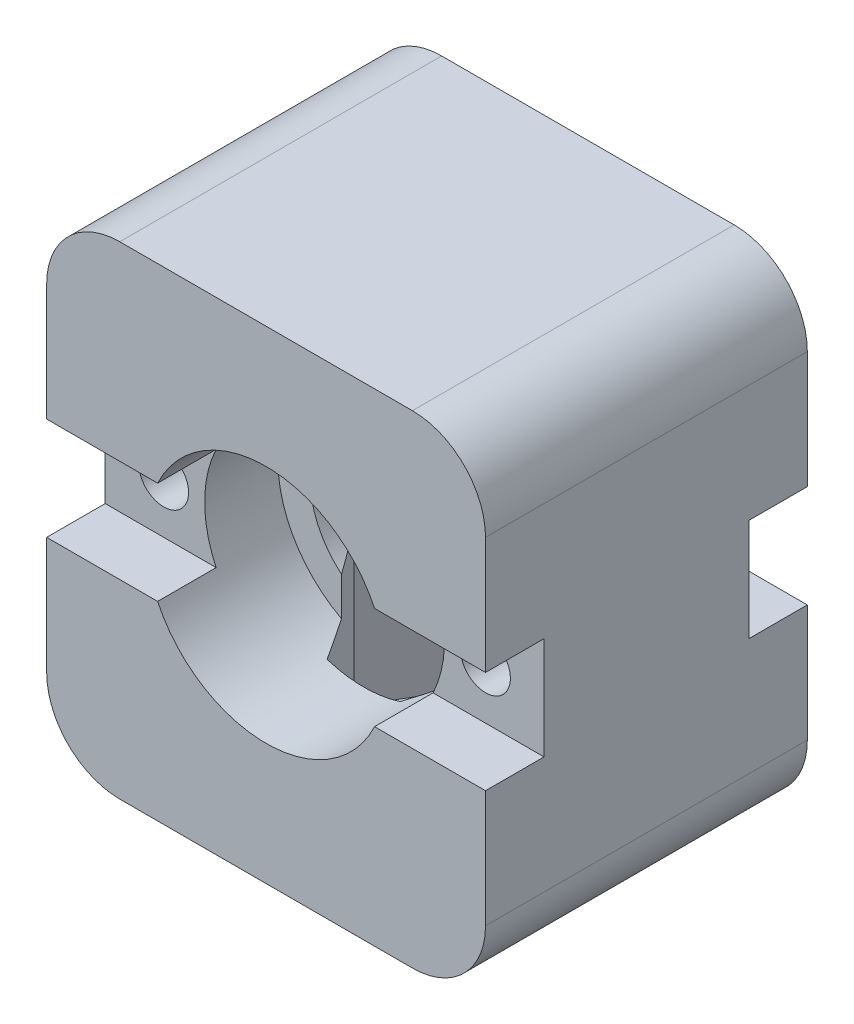
SolidWorks part; units mm, degrees
material "PLA"
ref_plane "Alzado" through (0, 0, 0) normal (0, 0, 1) x (1, 0, 0)
ref_plane "Planta" through (0, 0, 0) normal (0, 1, 0) x (1, 0, 0)
ref_plane "Vista lateral" through (0, 0, 0) normal (1, 0, 0) x (0, 0, -1)
sketch "Croquis2" plane through (0, 0, 0) normal (0, 0, 1) x (1, 0, 0)
  line L0 (-15, -1.5) -> (-15, 1.5)
  line L1 (10, -16.5) -> (-10, -16.5)
  line L2 (15, -11.5) -> (15, -1.5)
  line L3 (10, 16.5) -> (-10, 16.5)
  line L4 (-15, -11.5) -> (-15, -1.5)
  line L5 (15, -16.5) -> (-15, 16.5) construction
  line L6 (15, 16.5) -> (-15, -16.5) construction
  line L9 (-15, 1.5) -> (-15, 11.5)
  line L10 (0, 27.7977) -> (0, -27.7977) construction
  line L13 (15, 1.5) -> (15, 11.5)
  line L14 (15, -1.5) -> (15, 1.5)
  arc A0 (-15, -11.5) -> (-10, -16.5) centre (-10, -11.5) ccw
  arc A1 (10, -16.5) -> (15, -11.5) centre (10, -11.5) ccw
  arc A2 (15, 11.5) -> (10, 16.5) centre (10, 11.5) ccw
  arc A3 (-15, 11.5) -> (-10, 16.5) centre (-10, 11.5) cw
  point P0 (0, 0)
  point P30 (0, 0)
  dimension "D3" = 5
  dimension "D1" = 30
  dimension "D2" = 33
extrude "Saliente-Extruir2" add sketch "Croquis2" along normal blind 11 and the other way blind 11
sketch "Croquis4" plane through (0, 0, -11) normal (0, 0, -1) x (-1, 0, 0)
  line L0 (-11, 0) -> (11, 0) construction
  circle A0 centre (0, 0) radius 6
  circle A1 centre (-11, 0) radius 1.7
  circle A2 centre (11, 0) radius 1.7
  point P2 (0, 0)
  dimension "D1" = 3.4
  dimension "D2" = 12
  dimension "D3" = 22
extrude "Cortar-Extruir2" cut sketch "Croquis4" against normal blind 33
sketch "Croquis5" plane through (0, 0, 11) normal (0, 0, 1) x (1, 0, 0)
  circle A0 centre (0, 0) radius 8.2
  dimension "D1" = 16.4
extrude "Cortar-Extruir3" cut sketch "Croquis5" against normal blind 9
sketch "Croquis6" plane through (0, 0, 11) normal (0, 0, 1) x (1, 0, 0)
  line L1 (15.3, -3.5) -> (-15.3, -3.5)
  line L2 (15.3, -3.5) -> (15.3, 3.5)
  line L3 (15.3, 3.5) -> (-15.3, 3.5)
  line L4 (-15.3, -3.5) -> (-15.3, 3.5)
  line L5 (15.3, -3.5) -> (-15.3, 3.5) construction
  line L6 (15.3, 3.5) -> (-15.3, -3.5) construction
  point P0 (0, 0)
  dimension "D1" = 7
  dimension "D2" = 30.6
extrude "Cortar-Extruir4" cut sketch "Croquis6" against normal blind 4
sketch "Croquis8" plane through (0, 0, 0) normal (0, 1, 0) x (1, 0, 0)
  line L0 (-10, -11) -> (10, -11) construction
  line L1 (5, 0) -> (2.5, 4.3301)
  line L2 (2.5, 4.3301) -> (-2.5, 4.3301)
  line L3 (-2.5, 4.3301) -> (-5, 0)
  line L4 (-5, 0) -> (-2.5, -4.3301)
  line L5 (-2.5, -4.3301) -> (2.5, -4.3301)
  line L6 (2.5, -4.3301) -> (5, 0)
  circle A1 centre (0, 0) radius 5 construction
  dimension "D1" = 10
extrude "Cortar-Extruir6" cut sketch "Croquis8" against normal blind 14
sketch "Croquis9" plane through (0, -16.5, 0) normal (0, -1, 0) x (1, 0, 0)
  circle A0 centre (0, 0) radius 2.6
  dimension "D1" = 5.2
extrude "Cortar-Extruir7" cut sketch "Croquis9" against normal blind 5
mirror "Simetría1" about plane through (0, 0, 0) normal (0, 0, 1) of "Cortar-Extruir3", "Cortar-Extruir4"
